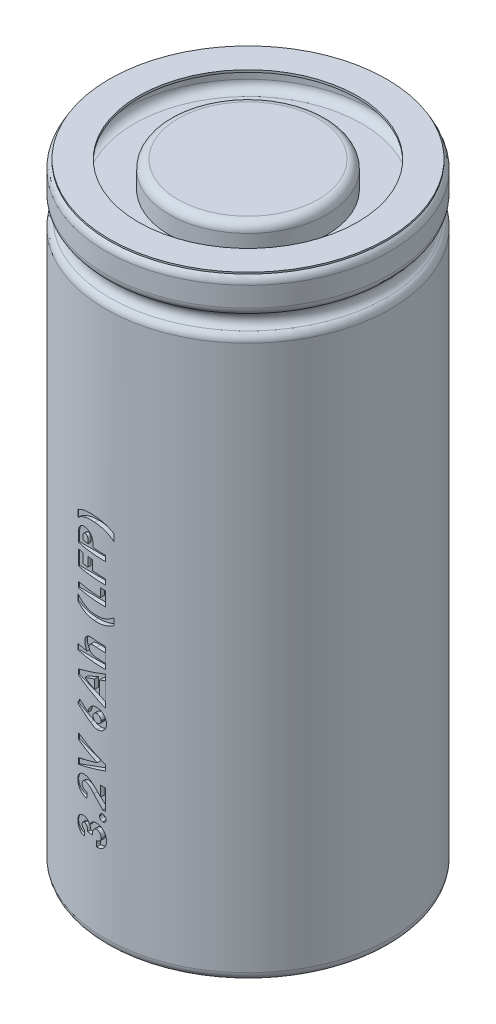
SolidWorks part; units mm, degrees
ref_plane "Front Plane" through (0, 0, 0) normal (0, 0, 1) x (1, 0, 0)
ref_plane "Top Plane" through (0, 0, 0) normal (0, 1, 0) x (1, 0, 0)
ref_plane "Right Plane" through (0, 0, 0) normal (1, 0, 0) x (0, 0, -1)
sketch "Sketch2" plane through (0, 0, 0) normal (0, 1, 0) x (1, 0, 0)
  circle A0 centre (0, 0) radius 16.25
  dimension "D1" = 32.5
extrude "Boss-Extrude1" add sketch "Sketch2" along normal blind 70
sketch "Sketch3" plane through (0, 70, 0) normal (0, 1, 0) x (1, 0, 0)
  circle A0 centre (0, 0) radius 14
  dimension "D1" = 28
extrude "Cut-Extrude1" cut sketch "Sketch3" against normal blind 3
sketch "Sketch4" plane through (0, 67, 0) normal (0, 1, 0) x (1, 0, 0)
  circle A0 centre (0, 0) radius 9
  dimension "D1" = 18
extrude "Boss-Extrude2" add sketch "Sketch4" along normal blind 3
sketch "Sketch5" plane through (0, 0, 0) normal (0, 0, 1) x (1, 0, 0)
  line L0 (16.25, 0) -> (16.25, 70) construction
  line L1 (16.25, 70) -> (-16.25, 70) construction
  line L2 (0, 0) -> (0, 16.3058) construction
  circle A0 centre (16.25, 65) radius 1
  dimension "D1" = 2
  dimension "D2" = 5
revolve "Cut-Revolve1" cut sketch "Sketch5" angle 360 about L2
fillet "Fillet1" radius 1 7 edges at (0, 0, 16.25) (0, 66, -16.25) (0, 64, 16.25) (0, 70, 16.25) (0, 70, 14) (0, 67, 14) (0, 70, 9)
sketch "Sketch6" plane through (0, 70, 0) normal (0, 1, 0) x (1, 0, 0)
  circle A0 centre (0, 0) radius 15.8332
  circle A1 centre (0, 0) radius 12.5
  dimension "D1" = 25
extrude "Boss-Extrude3" add sketch "Sketch6" against normal blind 0.25
ref_plane "Plane1" through (0, 0, 16.25) normal (0, 0, 1) x (1, 0, 0)
sketch "Sketch7" plane through (0, 0, 16.25) normal (0, 0, 1) x (1, 0, 0)
  line L0 (0, 9.3895) -> (0, 58.3555) construction
  text T0 "<b>3.2V 6Ah (LFP) </b>"
extrude "Cut-Extrude2" cut sketch "Sketch7" against normal blind 0.5
